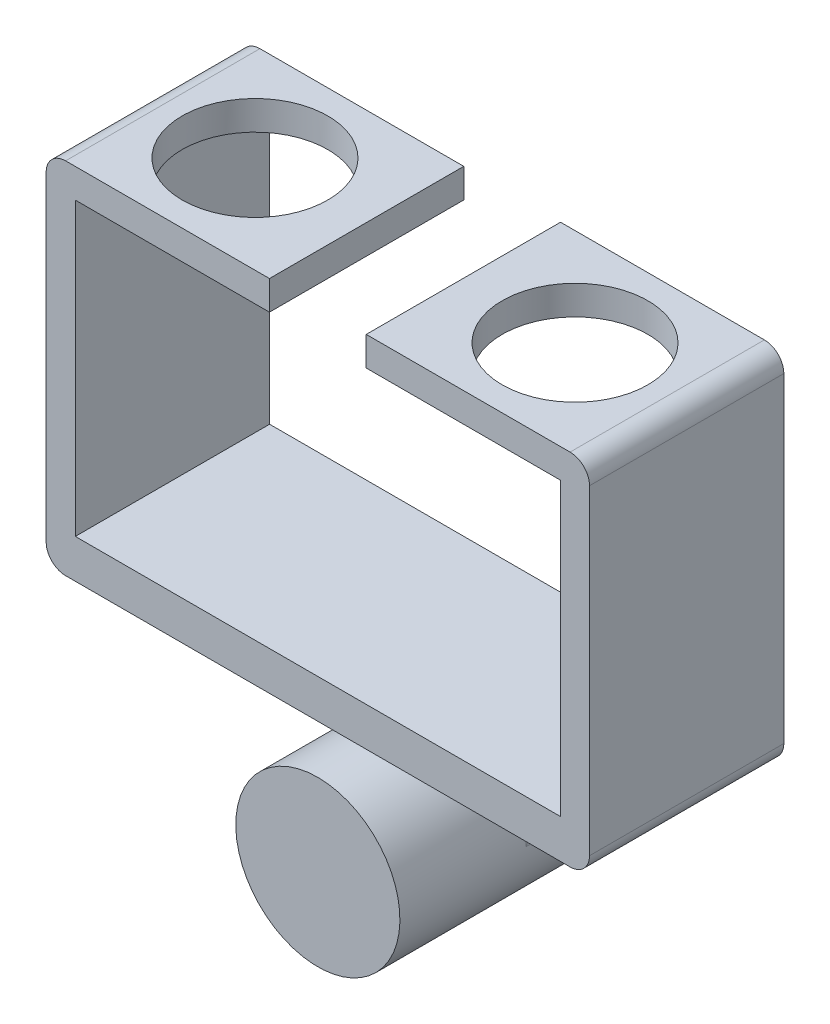
SolidWorks part; units mm, degrees
material "6061-T6 (SS)"
ref_plane "Front Plane" through (0, 0, 0) normal (0, 0, 1) x (1, 0, 0)
ref_plane "Top Plane" through (0, 0, 0) normal (0, 1, 0) x (1, 0, 0)
ref_plane "Right Plane" through (0, 0, 0) normal (1, 0, 0) x (0, 0, -1)
sketch "Sketch1" plane through (0, 0, 0) normal (0, 0, 1) x (1, 0, 0)
  line L0 (-35.5117, 17.0688) -> (35.5117, 17.0688)
  line L1 (35.5117, 17.0688) -> (35.5117, 64.0334)
  line L2 (35.5117, 64.0334) -> (6.3246, 64.0334)
  line L3 (6.3246, 64.0334) -> (6.3246, 60.2234)
  line L4 (6.3246, 60.2234) -> (31.7043, 60.2234)
  line L5 (31.7043, 60.2234) -> (31.7043, 22.1488)
  line L6 (31.7043, 22.1488) -> (-31.7043, 22.1488)
  line L7 (-31.7043, 22.1488) -> (-31.7043, 60.2234)
  line L8 (-31.7043, 60.2234) -> (-6.3246, 60.2234)
  line L9 (-6.3246, 60.2234) -> (-6.3246, 64.0334)
  line L10 (-6.3246, 64.0334) -> (-35.5117, 64.0334)
  line L11 (-35.5117, 64.0334) -> (-35.5117, 17.0688)
  line L12 (0, 0) -> (0, 17.0688) construction
  circle A0 centre (0, 0) radius 10.7287
  dimension "D1" = 21.4574
  dimension "D5" = 38.0746
  dimension "D6" = 71.0235
  dimension "D7" = 3.8075
  dimension "D8" = 3.81
  dimension "D11" = 5.08
  dimension "D12" = 17.0688
  dimension "D2" = 63.4086
  dimension "D3" = 29.1871
extrude "Boss-Extrude1" add sketch "Sketch1" along normal blind 25.4
sketch "Sketch2" plane through (0, 17.0688, 0) normal (0, -1, 0) x (1, 0, 0)
  line L0 (-10.7287, 25.4) -> (-10.7287, 0) construction
  line L1 (-10.7287, 0) -> (10.7287, 0)
  line L2 (-10.7287, 0) -> (-10.7287, 6.35)
  line L3 (-10.7287, 6.35) -> (10.7287, 6.35)
  line L4 (10.7287, 0) -> (10.7287, 6.35)
  line L5 (10.7287, 0) -> (10.7287, 25.4) construction
  line L6 (-10.7287, 0) -> (10.7287, 0) construction
  dimension "D1" = 6.35
extrude "Boss-Extrude2" add sketch "Sketch2" along normal blind 17.0688
sketch "Sketch3" plane through (0, 0, 0) normal (1, 0, 0) x (0, 0, -1)
  line L0 (-25.4, 10.7287) -> (-6.35, 10.7287)
  line L3 (-6.35, 10.7287) -> (-25.4, 10.7287) construction
split line "Split Line1"
sketch "Sketch4" plane through (0, 64.0334, 0) normal (0, 1, 0) x (1, 0, 0)
  line L0 (35.5117, 0) -> (6.3246, 0) construction
  line L1 (35.5117, -25.4) -> (35.5117, 0) construction
  line L2 (-6.3246, 0) -> (-35.5117, 0) construction
  circle A0 centre (20.9182, -12.7) radius 9.525
  circle A1 centre (-20.9182, -12.7) radius 9.525
  point P4 (20.9182, 0)
  point P7 (35.5117, -12.7)
  point P10 (-21.7754, -12.7)
  point P11 (0, 0)
  point P14 (-20.9182, 0)
  dimension "D1" = 19.05
  dimension "D2" = 19.05
extrude "Cut-Extrude1" cut sketch "Sketch4" against normal up to next
fillet "Fillet1" radius 2.54 9 edges at (-7.5863, 7.5863, 6.35) (35.5117, 17.0688, 12.7) (35.5117, 64.0334, 12.7) (-35.5117, 64.0334, 12.7) (-35.5117, 17.0688, 12.7) (7.5863, 7.5863, 6.35) (10.7287, 17.0688, 3.175) (-10.7287, 17.0688, 3.175) (0, 17.0688, 6.35)
equation "\"SF\"= 4"
equation "\"YieldS\"= 40000"
equation "\"E\"= 10 ^ 6"
equation "\"b\"= 1"
equation "\"F\"= 500"
equation "\"La\"= 1"
equation "\"Za\"= \"F\" * \"SF\" * \"La\" * 2 / ( \"YieldS\" * 2 )"
equation "\"Defl\"= 0.005"
equation "\"Da\"= ( ( 16 * \"F\" * \"La\" ) / ( \"E\" * \"Defl\" * pi ) ) ^ ( 1 / 4 )"
equation "\"Lb\"= .672"
equation "\"bb\"= \"Da\""
equation "\"hb\"= ( 2 * \"F\" * \"Lb\" ) / ( \"bb\" * \"E\" * \"Defl\" )"
equation "\"Lc\"= 2.4964"
equation "\"hc\"= ( ( 24 * \"F\" * ( \"Lc\" ^ 3 ) ) / ( 48 * \"E\" * \"b\" * \"Defl\" ) ) ^ ( 1 / 3 )"
equation "\"Ld\"= 1.499"
equation "\"hd\"= ( \"F\" * \"Ld\" ) / ( \"E\" * \"b\" * \"Defl\" )"
equation "\"Le\"= 0.9992"
equation "\"he\"= ( ( \"SF\" * \"F\" * \"Le\" * 3 ) / ( \"YieldS\" * \"b\" ) ) ^ ( 1 / 2 )"
equation "\"D1@Sketch1\"=\"Da\""
equation "\"D12@Sketch1\"=\"Lb\""
equation "\"D11@Sketch1\"=.2"
equation "\"D5@Sketch1\"=\"Ld\""
equation "\"D8@Sketch1\"=.15"
equation "\"D7@Sketch1\"=\"hd\""
equation "\"D1@Sketch2\"=.25"
equation "\"D2@Sketch1\"=\"Lc\""
equation "\"bottomL\"= \"Lc\" + 2 * \"hd\""
equation "\"D6@Sketch1\"=\"bottomL\""
